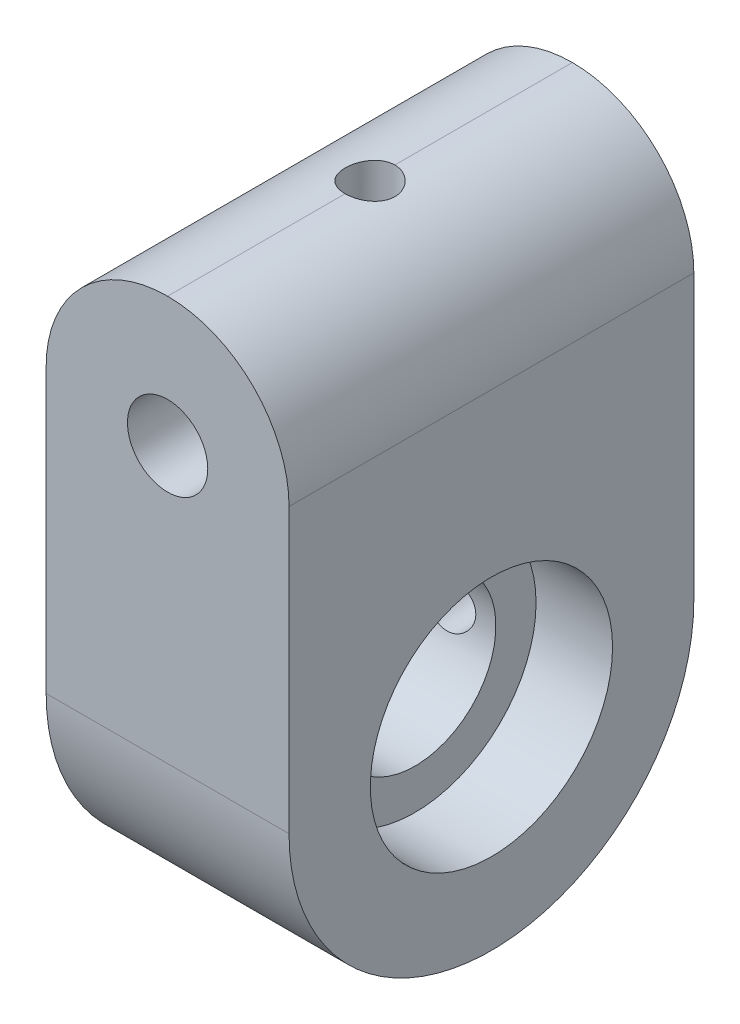
SolidWorks part; units mm, degrees
ref_plane "Front Plane" through (0, 0, 0) normal (0, 0, 1) x (1, 0, 0)
ref_plane "Top Plane" through (0, 0, 0) normal (0, 1, 0) x (1, 0, 0)
ref_plane "Right Plane" through (0, 0, 0) normal (1, 0, 0) x (0, 0, -1)
sketch "Sketch1" plane through (0, 0, 0) normal (1, 0, 0) x (0, 0, -1)
  circle A0 centre (0, 0) radius 9.5
  circle A1 centre (0, 0) radius 15.875
  dimension "D1" = 19
  dimension "D2" = 31.75
extrude "Boss-Extrude1" add sketch "Sketch1" along normal blind 6
sketch "Sketch2" plane through (0, 0, 0) normal (-1, 0, 0) x (0, 0, 1)
  circle A0 centre (0, 0) radius 6.35
  circle A1 centre (0, 0) radius 15.875
  circle A2 centre (0, 0) radius 15.875
  circle M3 centre (0, 0) radius 15.875
  circle M4 centre (0, 0) radius 9.5
  dimension "D2" = 12.7
  dimension "D1" = 0
extrude "Boss-Extrude2" add sketch "Sketch2" along normal blind 13.05 contours M3 M4 | A0 M4 region at (0, 0, -15.426) region at (0, 0, -9.2313)
sketch "Sketch3" plane through (-13.05, 0, 0) normal (-1, 0, 0) x (0, 0, 1)
  line L0 (0, 15.875) -> (0, -15.875) construction
  line L1 (0, 0) -> (19.648, 0) construction
  circle A0 centre (0, 12.7) radius 1.95
  circle A1 centre (0, 0) radius 15.875
  circle A2 centre (0, 0) radius 15.875
  circle A3 centre (0, -12.7) radius 1.95
  dimension "D2" = 3.9
  dimension "D3" = 12.7
  dimension "D1" = 0
extrude "Cut-Extrude1" cut sketch "Sketch3" against normal blind 10.16 contours A3 | A0 region at (-13.05, 12.7, 0) region at (-13.05, -12.7, 0)
ref_plane "Plane2" through (0, 0, -15.875) normal (0, 0, 1) x (1, 0, 0)
sketch "Sketch5" plane through (0, 0, -15.875) normal (0, 0, 1) x (1, 0, 0)
  line L0 (-13.05, 15.875) -> (-13.05, -15.875) construction
  line L1 (6, -15.875) -> (6, 15.875) construction
  line L2 (-13.05, 15.875) -> (-13.05, -15.875)
  line L3 (6, -15.875) -> (6, 15.875)
  line L4 (-13.05, 0) -> (6, 0) construction
  circle A0 centre (-3.525, 0) radius 1.95
  dimension "D1" = 3.9
extrude "Cut-Extrude3" cut sketch "Sketch5" along normal up to surface (9.525 mm away) contours A0 L4 | L4 A0 region at (-3.525, 0.8276, -15.875) region at (-3.525, -0.8276, -15.875) up to face at (-13.05, 0, 6.35)
sketch "Sketch6" plane through (-13.05, 0, 0) normal (-1, 0, 0) x (0, 0, 1)
  line L0 (0, 0) -> (0, 31.0805) construction
  line L1 (-15.875, 0) -> (-15.875, 31.75)
  line L2 (-15.875, 31.75) -> (15.875, 31.75)
  line L3 (15.875, 0) -> (15.875, 31.75)
  circle A1 centre (0, 0) radius 15.875
  circle A2 centre (0, 0) radius 15.875
  point P9 (0, 31.75)
  circle M6 centre (0, 0) radius 15.875
  dimension "D2" = 31.75
  dimension "D3" = 15.875
  dimension "D1" = 0
extrude "Boss-Extrude3" add sketch "Sketch6" against normal up to surface (19.05 mm away) contours L3 L2 L1 A2 M6 region at (-13.05, 21.7835, 0) up to face at (6, 0, -15.875)
sketch "Sketch7" plane through (0, 0, 15.875) normal (0, 0, 1) x (1, 0, 0)
  line L0 (6, 31.75) -> (-13.05, 31.75) construction
  line L1 (-3.525, 31.75) -> (-3.525, 21.59) construction
  line L2 (6, 0) -> (-13.05, 0) construction
  circle A0 centre (-3.525, 21.59) radius 3.15
  dimension "D1" = 6.3
  dimension "D2" = 21.59
extrude "Cut-Extrude4" cut sketch "Sketch7" against normal up to surface (31.75 mm away) contours A0 region at (-3.525, 21.59, 15.875) up to face at (-3.525, 10.5833, -15.875)
sketch "Sketch8" plane through (0, 31.75, 0) normal (0, 1, 0) x (1, 0, 0)
  line L0 (6, 15.875) -> (-13.05, 15.875) construction
  line L1 (-3.525, 15.875) -> (-3.525, 0) construction
  line L2 (-3.525, 0) -> (6, 0) construction
  line L3 (6, 15.875) -> (6, -15.875) construction
  circle A0 centre (-3.525, 0) radius 1.95
  dimension "D1" = 3.9
extrude "Cut-Extrude5" cut sketch "Sketch8" against normal up to surface (7.01 mm away) contours A0 region at (-3.525, 31.75, 0) up to face at (-0.375, 21.59, -15.875)
fillet "Fillet1" radius 9.525 2 edges at (6, 31.75, 0) (-13.05, 31.75, 0)
sketch "Sketch9" plane through (0, 0, -15.875) normal (0, 0, -1) x (-1, 0, 0)
  line L0 (1.575, 0) -> (5.475, 0) construction
  circle A0 centre (3.525, 0) radius 1.95
  point P4 (3.525, 0)
  dimension "D1" = 3.9
extrude "Cut-Extrude6" cut sketch "Sketch9" against normal up to surface (22.225 mm away) up to face at (0, 0, 6.35)
